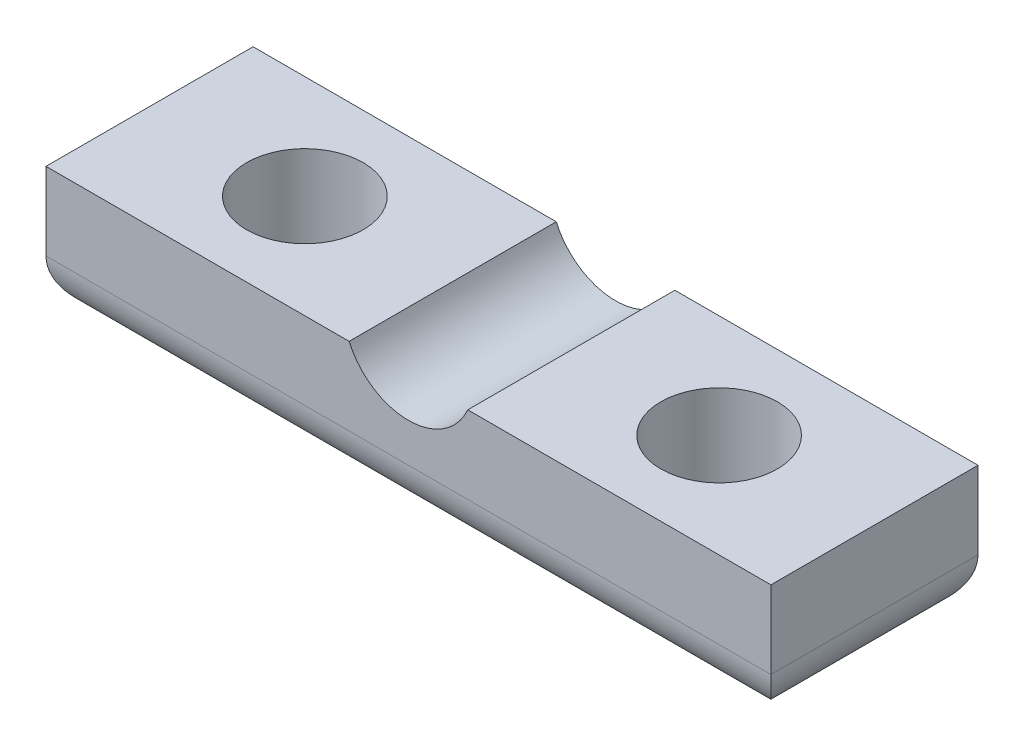
SolidWorks part; units mm, degrees
ref_plane "Front Plane" through (0, 0, 0) normal (0, 0, 1) x (1, 0, 0)
ref_plane "Top Plane" through (0, 0, 0) normal (0, 1, 0) x (1, 0, 0)
ref_plane "Right Plane" through (0, 0, 0) normal (1, 0, 0) x (0, 0, -1)
sketch "Sketch1" plane through (0, 0, 0) normal (0, 1, 0) x (1, 0, 0)
  line L0 (14, 0) -> (14, 8) construction
  line L1 (0, 8) -> (28, 8)
  line L2 (0, 8) -> (0, 0)
  line L3 (0, 0) -> (28, 0)
  line L4 (28, 8) -> (28, 0)
  circle A0 centre (6, 4) radius 2.25
  circle A1 centre (22, 4) radius 2.25
  dimension "D3" = 4.5
  dimension "D4" = 4.5
  dimension "D1" = 28
  dimension "D2" = 8
  dimension "D5" = 8
  dimension "D6" = 8
  dimension "D7" = 4
extrude "Boss-Extrude1" add sketch "Sketch1" along normal blind 5
sketch "Sketch2" plane through (0, 0, 0) normal (0, 0, 1) x (1, 0, 0)
  line L0 (11.5, 6) -> (16.5, 6)
  line L1 (16.5, 6) -> (28, 6) construction
  line L2 (28, 5) -> (28, 0) construction
  line L3 (0, 5) -> (0, 0) construction
  line L4 (0, 5) -> (28, 5) construction
  line L5 (0, 6) -> (11.5, 6) construction
  line L6 (0, 0) -> (28, 0) construction
  arc A0 (11.5, 6) -> (16.5, 6) centre (14, 6) ccw
  arc A1 (16.5, 6) -> (11.5, 6) centre (14, 6) ccw construction
  point P15 (14, 0)
  dimension "D1" = 5
  dimension "D2" = 1
extrude "Cut-Extrude1" cut sketch "Sketch2" against normal up to next
fillet "Fillet1" radius 2 4 edges at (14, 0, -8) (0, 0, -4) (28, 0, -4) (14, 0, 0)
